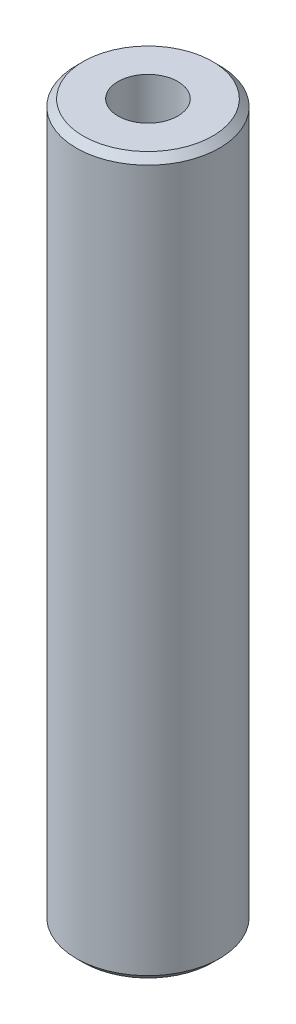
SolidWorks part; units mm, degrees
ref_plane "Front Plane" through (0, 0, 0) normal (0, 0, 1) x (1, 0, 0)
ref_plane "Top Plane" through (0, 0, 0) normal (0, 1, 0) x (1, 0, 0)
ref_plane "Right Plane" through (0, 0, 0) normal (1, 0, 0) x (0, 0, -1)
sketch "Sketch1" plane through (0, 0, 0) normal (0, 1, 0) x (1, 0, 0)
  circle A0 centre (0, 0) radius 60
  dimension "SHAFT_OD" = 120
extrude "Boss-Extrude1" add sketch "Sketch1" along normal blind 600
sketch "Sketch2" plane through (0, 0, 0) normal (0, 1, 0) x (1, 0, 0)
  circle A0 centre (0, 0) radius 25.0959
  dimension "BORE_D" = 50.1919
extrude "Cut-Extrude1" cut sketch "Sketch2" along normal through all
chamfer "Chamfer1" distance 5.8103 angle 45 2 edges at (0, 600, 60) (0, 0, 60)
